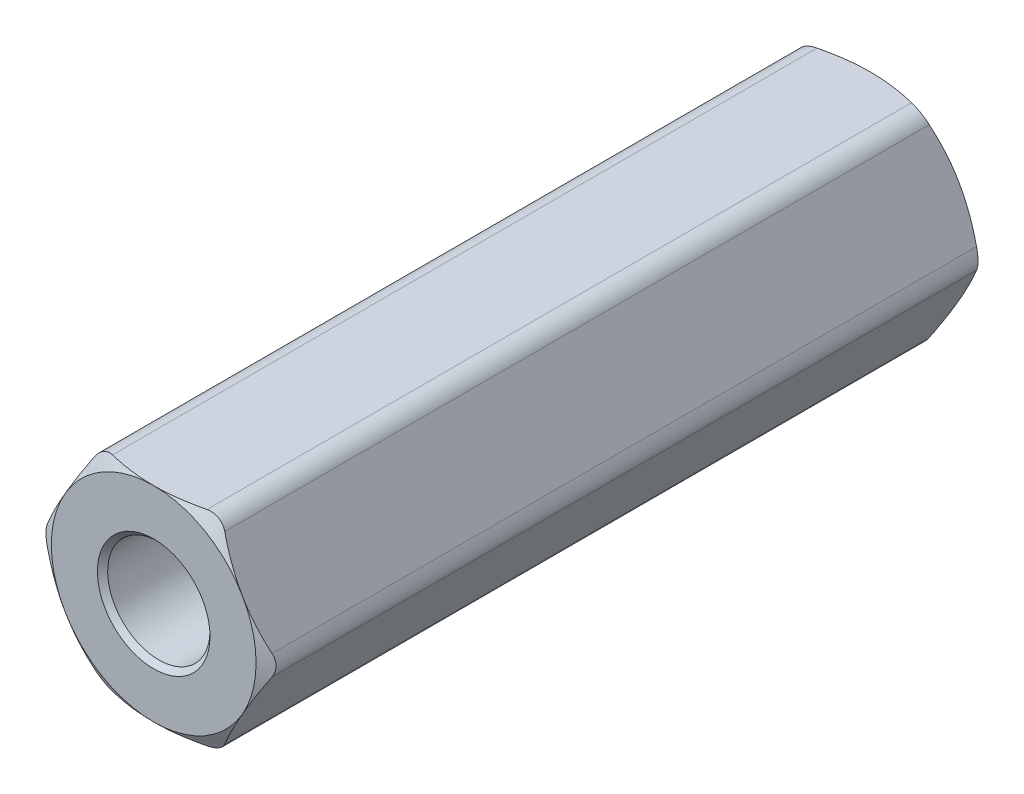
SolidWorks part; units mm, degrees
ref_plane "Front Plane" through (0, 0, 0) normal (0, 0, 1) x (1, 0, 0)
ref_plane "Top Plane" through (0, 0, 0) normal (0, 1, 0) x (1, 0, 0)
ref_plane "Right Plane" through (0, 0, 0) normal (1, 0, 0) x (0, 0, -1)
sketch "Sketch1" plane through (0, 0, 0) normal (0, 0, 1) x (1, 0, 0)
  line L0 (0, 0) -> (7.3323, 0) construction
  line L1 (3.6662, -6.35) -> (7.3323, 0)
  line L2 (7.3323, 0) -> (3.6662, 6.35)
  line L3 (3.6662, 6.35) -> (-3.6662, 6.35)
  line L4 (-3.6662, 6.35) -> (-7.3323, 0)
  line L5 (-7.3323, 0) -> (-3.6662, -6.35)
  line L6 (-3.6662, -6.35) -> (3.6662, -6.35)
  circle A0 centre (0, 0) radius 6.35 construction
  point P10 (0, -6.35)
  dimension "Hex Size" = 12.7
sketch "Sketch2" plane through (0, 0, 0) normal (1, 0, 0) x (0, 0, -1)
  line L0 (-6.35, 0) -> (-22.225, 0) construction
  line L3 (-6.35, 3.175) -> (-6.35, -3.175) construction
  line L4 (-23.4156, 3.3125) -> (-22.7806, 2.2126) construction
  line L5 (-22.7806, 2.2126) -> (-22.1456, 3.3125) construction
  line L6 (-22.1456, 3.3125) -> (-23.4156, 3.3125) construction
  line L7 (-23.3362, 3.175) -> (-22.225, 3.175) construction
  line L8 (-22.86, 2.3501) -> (-22.7012, 2.3501) construction
  line L9 (-22.7806, 2.3501) -> (-22.7806, 2.2126) construction
  line L10 (-22.7806, 3.175) -> (-22.7806, 3.3125) construction
  line L11 (22.225, 6.35) -> (-22.225, 6.35) construction
  point P6 (0, 6.35)
  point P9 (-6.35, 0)
  dimension "Minimum Thread Length" = 15.875
  dimension "Thread Size" = 6.35
  dimension "Thread Pitch" = 1.27
  dimension "Thread Pitch (B)/8" = 0.1588
  dimension "Length" = 44.45
sketch "Sketch3" plane through (0, 0, 0) normal (1, 0, 0) x (0, 0, -1)
  line L1 (-6.35, 3.175) -> (-6.35, 0)
  line L2 (22.225, 6.35) -> (22.225, 3.175)
  line L6 (22.225, 6.35) -> (22.225, 3.175)
  line L8 (22.225, 3.175) -> (6.35, 3.175)
  line L9 (-21.9075, 3.175) -> (-22.225, 3.4925)
  line L10 (0, 6.35) -> (22.225, 6.35)
  line L11 (-22.225, 3.4925) -> (-22.225, 6.35)
  line L12 (-22.225, 6.35) -> (0, 6.35)
  line L13 (-6.35, 0) -> (6.35, 0)
  line L14 (6.35, 0) -> (6.35, 3.175)
  line L16 (-6.35, 3.175) -> (-21.9075, 3.175)
  point P5 (-22.225, -6.35)
  dimension "D1" = 45
  dimension "D3" = 0.3175
revolve "Revolve1" add sketch "Sketch3" angle 360 about L0
sketch "Sketch4" plane through (0, 0, 0) normal (0, 0, 1) x (1, 0, 0)
  line L0 (0, 6.35) -> (0, 3.175) construction
  line L1 (-3.6662, 6.35) -> (-7.3323, 0)
  line L2 (-7.3323, 0) -> (-3.6662, -6.35)
  line L3 (-3.6662, -6.35) -> (3.6662, -6.35)
  line L4 (3.6662, -6.35) -> (7.3323, 0)
  line L5 (7.3323, 0) -> (3.6662, 6.35)
  line L6 (3.6662, 6.35) -> (-3.6662, 6.35)
  line L7 (3.6662, -6.35) -> (7.3323, 0) construction
  circle A0 centre (0, 0) radius 6.35 construction
  circle A1 centre (0, 0) radius 4.7625
  circle A2 centre (0, 0) radius 6.35 construction
  point P16 (0, 4.7625)
extrude "Boss-Extrude1" add sketch "Sketch4" against normal mid plane 44.45
sketch "Sketch5" plane through (0, 0, 22.225) normal (0, 0, 1) x (1, 0, 0)
  line L0 (0, 3.175) -> (0, -3.175) construction
  line L1 (0, 3.175) -> (0, -3.175) construction
  circle A0 centre (0, 0) radius 6.35
  circle A1 centre (0, 0) radius 6.35 construction
  point P11 (0, -3.175)
extrude "Cut-Extrude1" cut sketch "Sketch5" against normal through all draft 60 flip side to cut
sketch "Sketch6" plane through (0, 0, -22.225) normal (0, 0, -1) x (-1, 0, 0)
  circle A0 centre (0, 0) radius 6.35
  circle A1 centre (0, 0) radius 6.35 construction
extrude "Cut-Extrude2" cut sketch "Sketch6" against normal through all draft 60 flip side to cut
fillet "Fillet1" radius 1.27 6 edges at (3.6662, 6.35, 0) (-7.3323, 0, 0) (-3.6662, -6.35, 0) (3.6662, -6.35, 0) (7.3323, 0, 0) (-3.6662, 6.35, 0)
sketch "Drawing 1" plane through (0, 0, 0) normal (1, 0, 0) x (0, 0, -1)
  line L0 (-6.35, -3.175) -> (-22.225, -3.175) construction
  line L1 (-6.35, 3.175) -> (-22.225, 3.175) construction
  line L2 (22.225, 3.175) -> (6.35, 3.175) construction
  line L3 (-6.35, 0) -> (-22.225, 0) construction
  line L4 (6.35, 3.175) -> (6.35, -3.175) construction
  line L5 (6.35, -3.175) -> (22.225, -3.175) construction
  line L6 (-6.35, 3.175) -> (-6.35, -3.175) construction
split "Split1" [suppressed] bodies to split 107
sketch "Sketch7" [suppressed] plane through (0, 0, 6.35) normal (0, 0, -1) x (-1, 0, 0)
  circle A0 centre (0, 0) radius 3.4925
extrude "Boss-Extrude2" [suppressed] add sketch "Sketch7" along normal up to surface (15.875 mm away) up to face at (0, 3.4925, 22.225)
sketch "Sketch8" [suppressed] plane through (0, 0, 0) normal (1, 0, 0) x (0, 0, -1)
  line L0 (-6.35, 0) -> (-22.225, 0) construction
  line L1 (-6.35, 3.175) -> (-22.225, 3.175)
  line L2 (-6.35, 3.175) -> (-6.35, 0)
  line L3 (-6.35, 0) -> (-22.225, 0)
  line L4 (-22.225, 3.175) -> (-22.225, 0)
revolve "Revolve2" [suppressed] add sketch "Sketch8" angle 360 about L0
sketch "Sketch9" [suppressed] plane through (0, 0, 22.225) normal (0, 0, 1) x (1, 0, 0)
  circle A0 centre (0, 0) radius 3.175
  circle A1 centre (0, 0) radius 3.175 construction
sketch "Sketch10" [suppressed] plane through (0, 0, 0) normal (1, 0, 0) x (0, 0, -1)
  line L0 (-22.86, 2.3501) -> (-22.7012, 2.3501)
  line L1 (-22.7012, 2.3501) -> (-22.1853, 3.2437)
  line L2 (-22.7806, 2.2126) -> (-22.1456, 3.3125) construction
  line L3 (-22.1853, 3.2437) -> (-23.3759, 3.2437)
  line L4 (-23.4156, 3.3125) -> (-22.7806, 2.2126) construction
  line L5 (-23.3759, 3.2437) -> (-22.86, 2.3501)
  line L6 (-22.7806, 3.175) -> (-22.7806, 3.3125) construction
  point P12 (-22.7806, 3.2437)
curve "Helix/Spiral1" [suppressed] pitch 1.27 height 17.145 turns 13.5
sweep "Cut-Sweep1" [suppressed] cut profiles "Sketch10" path "Helix/Spiral1"
combine bodies "Combine1" [suppressed] operation type subtract main body 113 bodies to subtract 114
ref_plane "Plane1" [suppressed] through (0, 0, 21.9075) normal (0, 0, 1) x (1, 0, 0)
sketch "Sketch11" [suppressed] plane through (0, 0, 22.225) normal (0, 0, 1) x (1, 0, 0)
  circle A0 centre (0, 0) radius 3.4925
extrude "Cut-Extrude3" [suppressed] cut sketch "Sketch11" against normal through all draft 45
pattern_circular "CirPattern1" [suppressed] count 2 over 360 about axis through (0, 0, 0) along (1, 0, 0) of bodies 116 118
combine bodies "Combine2" [suppressed] bodies to combine 116 121
equation "\"Thread Pitch (B)/8@Sketch2\" = \"Thread Pitch@Sketch2\" / 8"
equation "\"D1@Fillet1\" = \"Hex Size@Sketch1\" * .1"
equation "\"D3@Helix/Spiral1\" = \"Minimum Thread Length@Sketch2\" + \"Thread Pitch@Sketch2\""
equation "\"D4@Helix/Spiral1\" = \"Thread Pitch@Sketch2\""
equation "\"D1@Boss-Extrude1\" = \"Length@Sketch2\""
equation "\"D3@Sketch3\"=\"Thread Pitch@Sketch2\"*.25"
